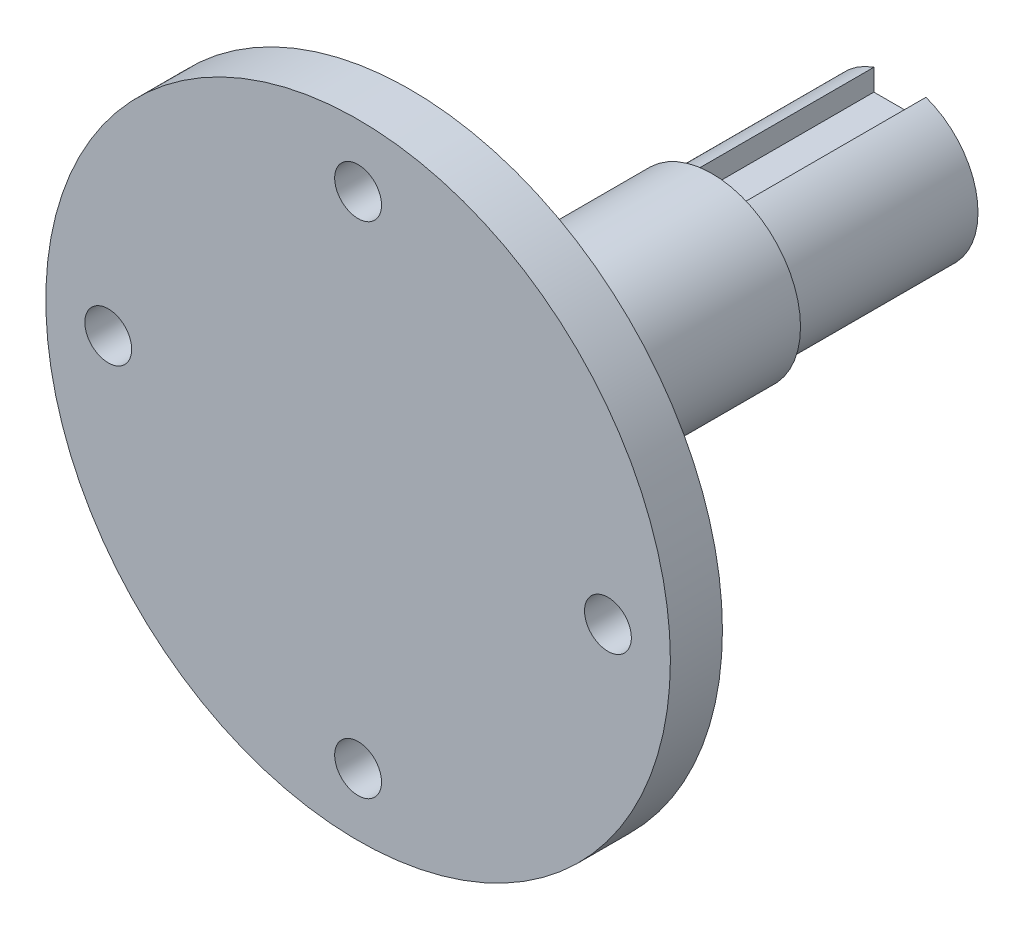
SolidWorks part; units mm, degrees
material "Plain Carbon Steel"
ref_plane "Front Plane" through (0, 0, 0) normal (0, 0, 1) x (1, 0, 0)
ref_plane "Top Plane" through (0, 0, 0) normal (0, 1, 0) x (1, 0, 0)
ref_plane "Right Plane" through (0, 0, 0) normal (1, 0, 0) x (0, 0, -1)
sketch "Sketch1" plane through (0, 0, 0) normal (0, 0, 1) x (1, 0, 0)
  circle A0 centre (0, 0) radius 7.5
  dimension "D1" = 15
extrude "Boss-Extrude1" add sketch "Sketch1" along normal blind 20.05
sketch "Sketch3" plane through (0, 0, 0) normal (0, 0, -1) x (-1, 0, 0)
  line L0 (0, 55) -> (0, -55) construction
  line L1 (-2.5, 5) -> (2.5, 5)
  line L2 (-2.5, 5) -> (-2.5, 10)
  line L3 (-2.5, 10) -> (2.5, 10)
  line L4 (2.5, 5) -> (2.5, 10)
  line L5 (-2.5, 5) -> (2.5, 10) construction
  line L6 (-2.5, 10) -> (2.5, 5) construction
  circle A0 centre (0, 0) radius 7.5 construction
  point P0 (0, 7.5)
  dimension "D1" = 2.5
  dimension "D2" = 5
extrude "Cut-Extrude1" cut sketch "Sketch3" against normal blind 21
sketch "Sketch6" plane through (0, 0, 20.05) normal (0, 0, 1) x (1, 0, 0)
  circle A0 centre (0, 0) radius 8.5
  dimension "D1" = 17
extrude "Boss-Extrude2" add sketch "Sketch6" along normal blind 24
sketch "Sketch7" plane through (0, 0, 44.05) normal (0, 0, 1) x (1, 0, 0)
  circle A0 centre (0, 0) radius 11.25
  dimension "D1" = 22.5
extrude "Boss-Extrude3" add sketch "Sketch7" along normal blind 5
sketch "Sketch8" plane through (0, 0, 49.05) normal (0, 0, 1) x (1, 0, 0)
  circle A0 centre (0, 0) radius 30
  dimension "D1" = 60
extrude "Boss-Extrude4" add sketch "Sketch8" along normal blind 5
fillet "Fillet1" radius 0.6 1 edges at (8.5, 0, 44.05)
fillet "Fillet2" radius 5 1 edges at (11.25, 0, 49.05)
hole_wizard "M4 Clearance Hole1" positions "Sketch9" profile "Sketch10" hole size "M4" standard "ANSI Metric" end condition through all
sketch "Sketch9" plane through (0, 0, 54.05) normal (0, 0, 1) x (1, 0, 0)
  circle A0 centre (0, 0) radius 24
  point P0 (0, 24)
  point P2 (0, -24)
  point P4 (24, 0)
  point P6 (-24, 0)
  dimension "D1" = 48
sketch "Sketch10" plane through (0, 24, 54.05) normal (1, 0, 0) x (0, -1, 0)
  line L0 (0, 0) -> (0, 54.05)
  line L1 (0, 54.05) -> (2.25, 54.05)
  line L2 (2.25, 54.05) -> (2.25, 0)
  line L5 (2.25, 0) -> (0, 0)
  line L11 (0, -6.35) -> (0, 107.95) construction
  dimension "Thru Hole Dia." = 4.5
  dimension "Thru Hole Depth" = 54.05
hole_wizard "Ø1.0mm Dowel Hole1" positions "Sketch11" profile "Sketch12" hole size "Ø1.0" standard "ANSI Metric"
sketch "Sketch11" plane through (0, 0, 0) normal (0, 0, -1) x (-1, 0, 0)
  point P0 (0, 0)
sketch "Sketch12" plane through (0, 0, 0) normal (1, 0, 0) x (0, 1, 0)
  line L0 (0, 0) -> (0, 8)
  line L1 (0, 8) -> (4.1275, 8)
  line L2 (4.1275, 8) -> (4.1275, 0)
  line L5 (4.1275, 0) -> (0, 0)
  line L10 (0, 8) -> (-4.1275, 8) construction
  line L11 (0, -6.35) -> (0, 107.95) construction
  dimension "Hole Dia." = 8.255
  dimension "Hole Depth" = 8
  dimension "Drill Angle" = 180
sketch "Sketch13" plane through (0, 0, 0) normal (0, 0, -1) x (-1, 0, 0)
  circle A0 centre (0, 0) radius 7.5
  dimension "D1" = 15
extrude "Cut-Extrude2" cut sketch "Sketch13" against normal blind 2
hole_wizard "M6 Clearance Hole1" positions "Sketch14" profile "Sketch15" hole size "M6" standard "ANSI Metric"
sketch "Sketch14" plane through (0, 0, 8) normal (0, 0, -1) x (-1, 0, 0)
  point P0 (0, 0)
sketch "Sketch15" plane through (0, 0, 8) normal (1, 0, 0) x (0, 1, 0)
  line L0 (0, 0) -> (0, 12)
  line L1 (0, 12) -> (3.3, 12)
  line L2 (3.3, 12) -> (3.3, 0)
  line L5 (3.3, 0) -> (0, 0)
  line L10 (0, 12) -> (-3.3, 12) construction
  line L11 (0, -6.35) -> (0, 107.95) construction
  dimension "Hole Dia." = 6.6
  dimension "Hole Depth" = 12
  dimension "Drill Angle" = 180
